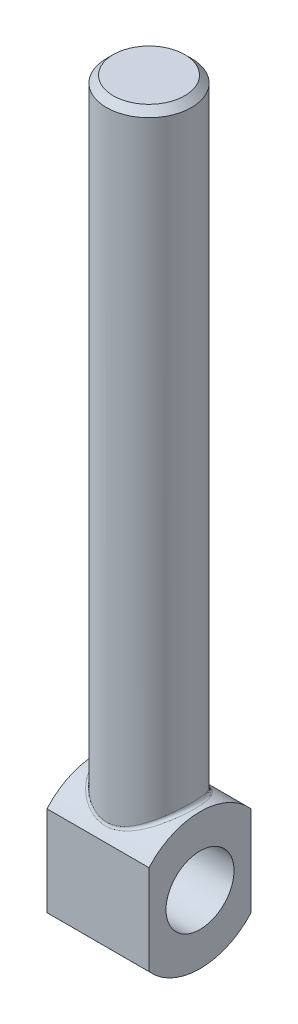
SolidWorks part; units mm, degrees
material "AISI 304"
ref_plane "Front Plane" through (0, 0, 0) normal (0, 0, 1) x (1, 0, 0)
ref_plane "Top Plane" through (0, 0, 0) normal (0, 1, 0) x (1, 0, 0)
ref_plane "Right Plane" through (0, 0, 0) normal (1, 0, 0) x (0, 0, -1)
sketch "Sketch1" plane through (0, 0, 0) normal (0, 1, 0) x (1, 0, 0)
  circle A0 centre (0, 0) radius 2.5
  dimension "D1" = 5
extrude "Boss-Extrude1" add sketch "Sketch1" along normal blind 40
cosmetic thread "Cosmetic Thread1" parameters "D1"=5, "D2"=4.11
sketch "Sketch2" plane through (0, 0, 0) normal (1, 0, 0) x (0, 0, -1)
  circle A0 centre (0, 0) radius 4
  dimension "D1" = 8
extrude "Boss-Extrude2" add sketch "Sketch2" along normal mid plane 6
sketch "Sketch3" plane through (-3, 0, 0) normal (-1, 0, 0) x (0, 0, 1)
  line L1 (-3, -4) -> (3, -4)
  line L2 (-3, -4) -> (-3, 4)
  line L3 (-3, 4) -> (3, 4)
  line L4 (3, -4) -> (3, 4)
  line L5 (-3, -4) -> (3, 4) construction
  line L6 (-3, 4) -> (3, -4) construction
  circle A1 centre (0, 0) radius 4 construction
  circle A2 centre (0, 0) radius 4
  point P0 (0, 0)
  circle M6 centre (0, 0) radius 4
  dimension "D1" = 6
extrude "Cut-Extrude1" cut sketch "Sketch3" against normal blind 6 contours L2 M6 | L4 M6 region at (-3, 0, -3.4046) region at (-3, 0, 3.4046)
sketch "Sketch5" plane through (-3, 0, 0) normal (-1, 0, 0) x (0, 0, 1)
  circle A0 centre (0, 0) radius 2
  dimension "D1" = 4
extrude "Cut-Extrude2" cut sketch "Sketch5" against normal through all
fillet "Fillet1" radius 0.2 1 edges at (-0.621, 3.1836, 2.4217)
chamfer "Chamfer1" distance 0.4 angle 45 1 edges at (0, 40, 2.5)
split "Split1" bodies to split 104 resulting bodies 105 106 split by face at (0.06, 3.0645, 2.5708)
